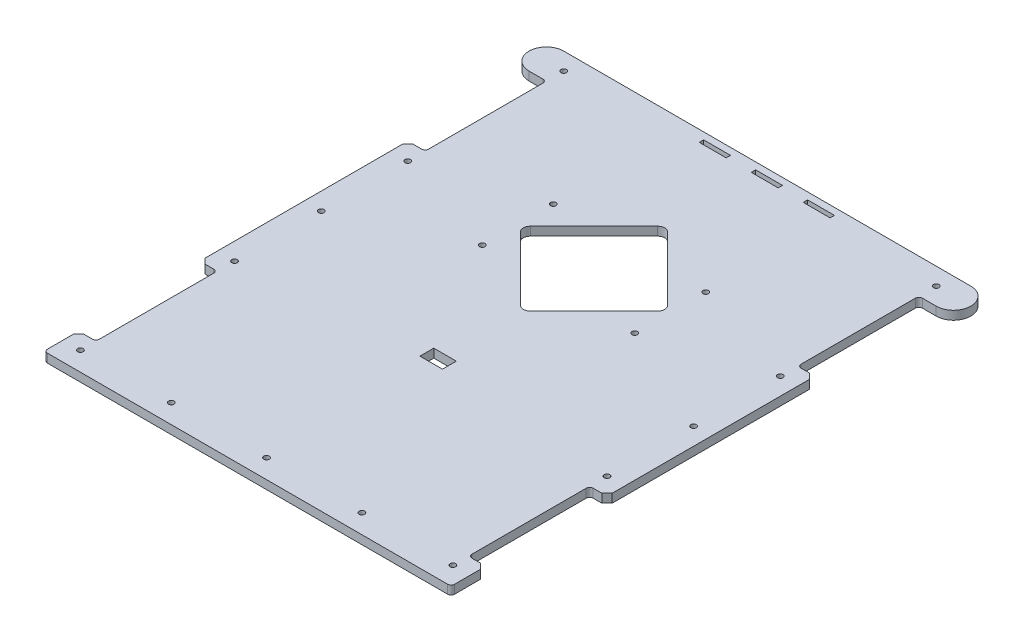
SolidWorks part; units mm, degrees
material "Teak"
ref_plane "Front Plane" through (0, 0, 0) normal (0, 0, 1) x (1, 0, 0)
ref_plane "Top Plane" through (0, 0, 0) normal (0, 1, 0) x (1, 0, 0)
ref_plane "Right Plane" through (0, 0, 0) normal (1, 0, 0) x (0, 0, -1)
sketch "Sketch1" plane through (0, 0, 0) normal (0, 1, 0) x (1, 0, 0)
  line L0 (0, 190) -> (0, -110) construction
  line L1 (-117.5, 0) -> (117.5, 0) construction
  line L2 (-117.5, -110) -> (117.5, -110)
  line L3 (117.5, -110) -> (117.5, -90)
  line L4 (117.5, -90) -> (107.5, -90)
  line L5 (107.5, -90) -> (107.5, -20)
  line L6 (107.5, -20) -> (117.5, -20)
  line L7 (117.5, -20) -> (117.5, 100)
  line L8 (117.5, 100) -> (107.5, 100)
  line L9 (107.5, 100) -> (107.5, 170)
  line L10 (107.5, 170) -> (127.5, 170)
  line L11 (-107.5, 170) -> (-127.5, 170)
  line L12 (-107.5, 100) -> (-107.5, 170)
  line L13 (-117.5, 100) -> (-107.5, 100)
  line L14 (-117.5, -20) -> (-117.5, 100)
  line L15 (-107.5, -20) -> (-117.5, -20)
  line L16 (-107.5, -90) -> (-107.5, -20)
  line L17 (-117.5, -90) -> (-107.5, -90)
  line L18 (-117.5, -110) -> (-117.5, -90)
  line L19 (127.5, 170) -> (127.5, 190)
  line L20 (127.5, 190) -> (-127.5, 190)
  line L21 (-127.5, 170) -> (-127.5, 190)
  point P5 (0, 0)
  dimension "D1" = 20
  dimension "D2" = 300
  dimension "D3" = 110
  dimension "D4" = 20
  dimension "D5" = 10
  dimension "D6" = 70
  dimension "D7" = 70
  dimension "D8" = 255
  dimension "D9" = 20
extrude "Boss-Extrude1" add sketch "Sketch1" along normal blind 5
fillet "Fillet3" 2 edges at (127.5, 2.5, -170) (127.5, 2.5, -190) type full round first side face at (117.5, 2.5, -170) second side face at (0, 2.5, -190) middle face at (127.5, 2.5, -180)
fillet "Fillet4" 2 edges at (-127.5, 2.5, -190) (-127.5, 2.5, -170) type full round first side face at (-5, 2.5, -190) second side face at (-117.5, 2.5, -170) middle face at (-127.5, 2.5, -180)
fillet "Fillet2" radius 2 10 edges at (107.5, 2.5, 20) (107.5, 2.5, -170) (107.5, 2.5, -100) (107.5, 2.5, 90) (-107.5, 2.5, -100) (-107.5, 2.5, 90) (-107.5, 2.5, 20) (-107.5, 2.5, -170) (-117.5, 2.5, 110) (117.5, 2.5, 110)
sketch "Sketch2" plane through (0, 5, 0) normal (0, 1, 0) x (1, 0, 0)
  line L0 (0, -110) -> (0, 90) construction
  line L1 (-115.5, -110) -> (115.5, -110) construction
  line L2 (107.5, 102) -> (107.5, 168) construction
  line L4 (117.5, -20) -> (117.5, 100) construction
  line L5 (117.5, -108) -> (117.5, -90) construction
  arc A0 (117.5, 170) -> (117.5, 190) centre (117.5, 180) ccw construction
  circle A1 centre (107.5, 180) radius 1.6
  circle A2 centre (107.5, 40) radius 1.6
  circle A3 centre (107.5, -99) radius 1.6
  circle A4 centre (-107.5, 40) radius 1.6
  circle A5 centre (-107.5, -99) radius 1.6
  circle A6 centre (-107.5, 40) radius 1.6
  circle A7 centre (-107.5, 180) radius 1.6
  circle A8 centre (107.5, 40) radius 1.6
  circle A9 centre (-107.5, 40) radius 1.6
  circle A10 centre (107.5, 40) radius 1.6
  circle A11 centre (0, -99) radius 1.6
  circle A12 centre (55, -99) radius 1.6
  circle A13 centre (-55, -99) radius 1.6
  circle A14 centre (-107.5, 90) radius 1.6
  circle A15 centre (107.5, 90) radius 1.6
  circle A16 centre (-107.5, -10) radius 1.6
  circle A17 centre (107.5, -10) radius 1.6
  point P17 (127.5, 180)
  point P26 (117.5, 40)
  point P30 (117.5, -99)
  point P47 (0, 0)
  dimension "D1" = 3.2
  dimension "D2" = 2
  dimension "D3" = 10
  dimension "D4" = 2
  dimension "D5" = 2
  dimension "D6" = 2
  dimension "D7" = 2
  dimension "D8" = 2
extrude "layer fix hole" cut sketch "Sketch2" against normal through all both and the other way through all contours A13 | A5 | A11 | A12 | A3 | A2 | A4 | A7 | A1 | A16 | A14 | A17 | A15
sketch "Sketch3" plane through (0, 5, 0) normal (0, 1, 0) x (1, 0, 0)
  line L0 (0, 190) -> (0, -110) construction
  line L1 (117.5, 190) -> (-117.5, 190) construction
  line L2 (-115.5, -110) -> (115.5, -110) construction
  line L3 (-39.598, 92.8284) -> (-2.8284, 129.598)
  line L8 (-50, 116.5) -> (50, 116.5) construction
  line L9 (-50, 116.5) -> (-50, 63.5) construction
  line L14 (-50, 63.5) -> (50, 63.5) construction
  line L15 (50, 116.5) -> (50, 63.5) construction
  line L21 (-50, 116.5) -> (50, 63.5) construction
  line L22 (-50, 63.5) -> (50, 116.5) construction
  line L23 (-39.598, 87.1716) -> (-2.8284, 50.402)
  line L24 (2.8284, 129.598) -> (39.598, 92.8284)
  line L25 (2.8284, 50.402) -> (39.598, 87.1716)
  line L26 (-35.0018, 90) -> (39.9515, 90) construction
  line L27 (0, 127.4767) -> (0, 52.5233) construction
  circle A12 centre (44, 110.5) radius 1.6
  circle A13 centre (44, 69.5) radius 1.6
  circle A14 centre (-44, 69.5) radius 1.6
  circle A15 centre (-44, 110.5) radius 1.6
  arc A16 (-2.8284, 129.598) -> (2.8284, 129.598) centre (0, 126.7696) cw
  arc A17 (39.598, 92.8284) -> (39.598, 87.1716) centre (36.7696, 90) cw
  arc A18 (-2.8284, 50.402) -> (2.8284, 50.402) centre (0, 53.2304) ccw
  arc A19 (-39.598, 87.1716) -> (-39.598, 92.8284) centre (-36.7696, 90) cw
  point P6 (0, 90)
  point P20 (0, 90)
  point P21 (-21.2132, 111.2132)
  point P22 (21.2132, 68.7868)
  dimension "D3" = 3.2
  dimension "D2" = 100
  dimension "D9" = 6
  dimension "D14" = 4
  dimension "D1" = 53
  dimension "D4" = 6
  dimension "D5" = 6
  dimension "D6" = 6
  dimension "D7" = 6
  dimension "D8" = 6
  dimension "D10" = 6
  dimension "D11" = 6
  dimension "D12" = 60
  dimension "D13" = 100
extrude "arm fix hole" cut sketch "Sketch3" against normal through all
sketch "Sketch4" plane through (0, 5, 0) normal (0, 1, 0) x (1, 0, 0)
  line L0 (0, 0) -> (0, 190) construction
  line L1 (117.5, 190) -> (-117.5, 190) construction
  line L2 (-32.75, 186) -> (-32.75, 183.5)
  line L3 (-72.75, 186) -> (-57.25, 186)
  line L4 (-72.75, 186) -> (-72.75, 183.5)
  line L5 (-72.75, 183.5) -> (-57.25, 183.5)
  line L6 (-57.25, 186) -> (-57.25, 183.5)
  line L7 (-17.25, 183.5) -> (-32.75, 183.5)
  line L8 (-17.25, 186) -> (-17.25, 183.5)
  line L9 (-17.25, 186) -> (-32.75, 186)
  line L10 (5, 97.0905) -> (5, 68.2589) construction
  line L11 (-85, 183.5) -> (85, 183.5) construction
  line L12 (-85, 183.5) -> (-85, 186) construction
  line L13 (-85, 186) -> (85, 186) construction
  line L14 (85, 183.5) -> (85, 186) construction
  line L15 (-25, 68.2589) -> (-25, 97.0905) construction
  line L16 (-65, 97.0905) -> (-65, 68.2589) construction
  line L17 (-25, 68.2589) -> (-25, 97.0905) construction
  line L18 (35, 68.2589) -> (35, 97.0905) construction
  line L20 (-2.75, 183.5) -> (12.75, 183.5)
  line L21 (-2.75, 183.5) -> (-2.75, 186)
  line L22 (-2.75, 186) -> (12.75, 186)
  line L23 (12.75, 183.5) -> (12.75, 186)
  line L24 (27.25, 183.5) -> (42.75, 183.5)
  line L25 (27.25, 183.5) -> (27.25, 186)
  line L26 (27.25, 186) -> (42.75, 186)
  line L27 (42.75, 183.5) -> (42.75, 186)
  point P17 (-65, 183.5)
  point P25 (-25, 183.5)
  point P35 (5, 186)
  point P36 (35, 186)
  dimension "D1" = 15.5
  dimension "D2" = 2.5
  dimension "D3" = 4
  dimension "D4" = 20
  dimension "D5" = 170
  dimension "D6" = 60
  dimension "D7" = 90
  dimension "D8" = 120
extrude "IR fix hole" cut sketch "Sketch4" against normal through all
chamfer "Chamfer1" distance 3 angle 45 6 edges at (117.5, 2.5, 20) (-117.5, 2.5, -100) (-117.5, 2.5, 20) (-117.5, 2.5, 90) (117.5, 2.5, -100) (117.5, 2.5, 90)
sketch "Sketch5" plane through (0, 5, 0) normal (0, 1, 0) x (1, 0, 0)
  line L1 (-57.25, 183.5) -> (-72.75, 183.5)
  line L2 (-57.25, 183.5) -> (-57.25, 186)
  line L3 (-57.25, 186) -> (-72.75, 186)
  line L4 (-72.75, 183.5) -> (-72.75, 186)
extrude "Boss-Extrude2" add sketch "Sketch5" against normal up to surface (5 mm away) up to face at (-65, 0, -184.75)
sketch "Sketch6" plane through (0, 5, 0) normal (0, 1, 0) x (1, 0, 0)
  line L0 (0, 110) -> (0, -110) construction
  line L1 (-115.5, -110) -> (115.5, -110) construction
  line L3 (6.5, -4) -> (-6.5, -4)
  line L4 (6.5, -4) -> (6.5, 4)
  line L5 (6.5, 4) -> (-6.5, 4)
  line L6 (-6.5, -4) -> (-6.5, 4)
  line L7 (6.5, -4) -> (-6.5, 4) construction
  line L8 (6.5, 4) -> (-6.5, -4) construction
  point P0 (0, 0)
  point P6 (0, 0)
  dimension "D1" = 13
  dimension "D2" = 8
extrude "Turn on/off Switch " cut sketch "Sketch6" against normal up to next
